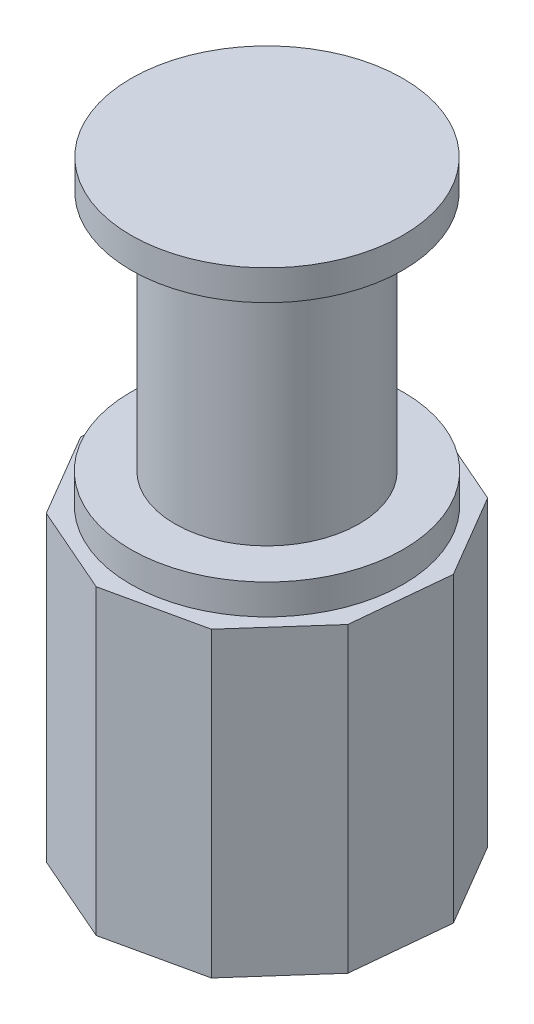
SolidWorks part; units mm, degrees
ref_plane "Спереди" through (0, 0, 0) normal (0, 0, 1) x (1, 0, 0)
ref_plane "Сверху" through (0, 0, 0) normal (0, 1, 0) x (1, 0, 0)
ref_plane "Справа" through (0, 0, 0) normal (1, 0, 0) x (0, 0, -1)
sketch "Эскиз2" plane through (0, 0, 0) normal (1, 0, 0) x (0, 0, -1)
  line L0 (0, -61.7012) -> (0, 99.8075) construction
  line L1 (0, 0) -> (45.1175, 0)
  line L2 (45.1175, 0) -> (45.1175, 10)
  line L3 (45.1175, 10) -> (30.4848, 10)
  line L4 (30.4848, 10) -> (30.4848, 90)
  line L5 (30.4848, 90) -> (45, 90)
  line L6 (45, 90) -> (45, 100)
  line L7 (45, 100) -> (0, 100)
  line L8 (0, 0) -> (0, 100)
revolve "Повернуть1" add sketch "Эскиз2" angle 360 about L0
sketch "Эскиз3" plane through (0, 0, 0) normal (0, -1, 0) x (1, 0, 0)
  line L0 (34.3373, -38.7295) -> (50.5441, -11.1499)
  line L1 (-5.0148, 51.5158) -> (-34.3373, 38.7295)
  line L2 (-34.3373, 38.7295) -> (-50.5441, 11.1499)
  line L3 (-50.5441, 11.1499) -> (-47.4448, -20.6886)
  line L4 (-47.4448, -20.6886) -> (-26.2232, -44.6248)
  line L5 (-26.2232, -44.6248) -> (5.0148, -51.5158)
  line L6 (5.0148, -51.5158) -> (34.3373, -38.7295)
  line L7 (50.5441, -11.1499) -> (47.4448, 20.6886)
  line L8 (47.4448, 20.6886) -> (26.2232, 44.6248)
  line L9 (26.2232, 44.6248) -> (-5.0148, 51.5158)
  circle A0 centre (0, 0) radius 49.226 construction
extrude "Бобышка-Вытянуть2" add sketch "Эскиз3" along normal blind 100
